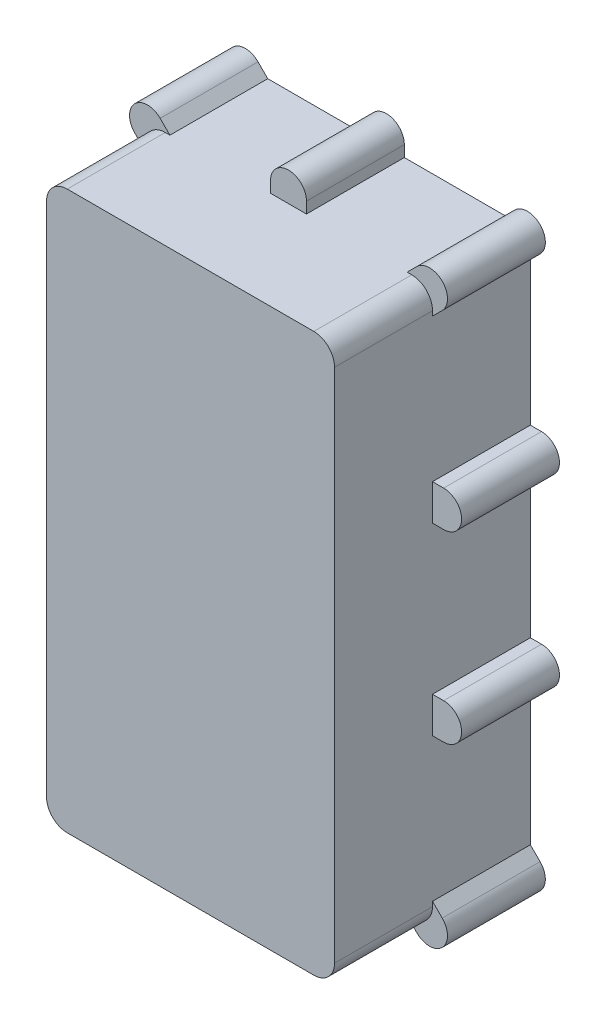
SolidWorks part; units mm, degrees
material "ABS"
ref_plane "X-Y Datum" through (0, 0, 0) normal (0, 0, 1) x (1, 0, 0)
ref_plane "X-Z Datum" through (0, 0, 0) normal (0, 1, 0) x (1, 0, 0)
ref_plane "Y-Z Datum" through (0, 0, 0) normal (1, 0, 0) x (0, 0, -1)
sketch "Sketch1" plane through (0, 0, 0) normal (0, 0, 1) x (1, 0, 0)
  line L0 (1.8162, 48.1563) -> (125.4513, 48.1563) construction
  line L1 (24.3593, 48.1563) -> (24.3593, 120.2923) construction
  line L3 (24.3593, 120.2923) -> (125.4513, 120.2923) construction
  line L8 (125.4513, 48.1563) -> (125.4513, 120.2923) construction
  line L33 (24.3593, 120.2923) -> (1.8162, 120.2923) construction
  line L34 (24.3593, 120.2923) -> (24.3593, 48.1563) construction
  line L35 (63.6337, 48.1563) -> (63.6337, 43.0763) construction
  line L36 (1.8162, 120.2923) -> (1.8162, 48.1563) construction
  line L41 (24.3593, 120.2923) -> (23.7243, 120.2923) construction
  line L42 (24.3593, 120.2923) -> (24.3593, 122.8323) construction
  line L44 (27.5343, 14.7553) -> (27.5343, 43.0763) construction
  line L45 (125.4513, 120.2923) -> (127.9913, 120.2923) construction
  line L46 (27.5343, 14.7553) -> (125.4513, 14.7553) construction
  line L47 (23.7243, 122.8323) -> (127.9913, 122.8323)
  line L48 (23.7243, 122.8323) -> (23.7243, -21.9477)
  line L49 (23.7243, -21.9477) -> (127.9913, -21.9477)
  line L50 (127.9913, 122.8323) -> (127.9913, -21.9477)
  line L51 (125.4513, 14.7553) -> (125.4513, 43.0763) construction
  line L52 (27.5343, 43.0763) -> (125.4513, 43.0763) construction
  line L53 (23.7243, 120.2923) -> (23.7243, 48.1563) construction
  circle A17 centre (30.4553, 114.1963) radius 2.1 construction
  circle A18 centre (119.8633, 115.2123) radius 2.1 construction
  circle A19 centre (119.6813, 54.2533) radius 2.1 construction
  circle A20 centre (29.4393, 53.2363) radius 2.1 construction
  circle A26 centre (31.9793, 18.4383) radius 2.1 construction
  circle A27 centre (31.9793, 39.3933) radius 2.1 construction
  circle A28 centre (120.6193, 28.8183) radius 2.1 construction
sketch "Sketch2" plane through (0, 0, 0) normal (0, 0, 1) x (1, 0, 0)
  line L4 (55.176, 122.8323) -> (127.9913, 122.8323)
  line L6 (55.176, 48.5244) -> (55.176, 50.9244) construction
  line L7 (55.176, -21.05) -> (127.9913, -21.05)
  line L8 (127.9913, 122.8323) -> (127.9913, -21.05)
  line L9 (55.176, 110.2103) -> (127.9913, -21.05) construction
  line L10 (55.176, -8.428) -> (127.9913, 122.8323) construction
  line L11 (55.176, 50.9244) -> (55.176, -21.05)
  line L12 (55.176, 50.9244) -> (55.176, 122.8323)
  circle A7 centre (88.0827, 6.45) radius 27.5
  circle A8 centre (88.0294, 95.3501) radius 27.5
  circle A9 centre (98.216, 50.8911) radius 6.477
  circle A10 centre (77.896, 50.9089) radius 6.477
  circle A11 centre (121.5143, 31.8208) radius 6.477
  circle A12 centre (115.996, 50.8756) radius 2.4
  circle A13 centre (55.176, 50.9244) radius 2.4
  point P14 (88.0827, 50.8911)
sketch "Sketch3" plane through (0, 0, 0) normal (0, 0, 1) x (1, 0, 0)
  line L7 (0, 0) -> (76.2, 0)
  line L10 (0, 0) -> (0, 158.75)
  line L11 (0, 158.75) -> (76.2, 158.75)
  line L12 (76.2, 0) -> (76.2, 158.75)
  dimension "D1" = 158.75
  dimension "D2" = 76.2
extrude "Boss-Extrude1" add sketch "Sketch3" along normal blind 53.975
shell "Shell1" thickness 6 removed face at (38.1, 79.375, 0) outward yes
fillet "Fillet1" radius 5.334 4 edges at (76.2, 158.75, 26.9875) (76.2, 0, 26.9875) (0, 0, 26.9875) (0, 158.75, 26.9875)
fillet "Fillet2" radius 6.35 4 edges at (-6, -6, 29.9875) (-6, 164.75, 29.9875) (82.2, 164.75, 29.9875) (82.2, -6, 29.9875)
sketch "Sketch6" plane through (0, 0, 0) normal (0, 0, -1) x (-1, 0, 0)
  line L8 (-5.334, 163.0327) -> (-70.866, 163.0327)
  line L9 (-80.4827, 153.416) -> (-80.4827, 5.334)
  line L10 (-70.866, -4.2827) -> (-5.334, -4.2827)
  line L11 (4.2827, 5.334) -> (4.2827, 153.416)
  line L12 (-79.2, 153.416) -> (-79.2, 5.334)
  line L13 (-70.866, -3) -> (-5.334, -3)
  line L14 (3, 5.334) -> (3, 153.416)
  line L15 (-5.334, 161.75) -> (-70.866, 161.75)
  line L16 (-79.2, 153.416) -> (-79.2, 5.334) construction
  line L17 (-70.866, -3) -> (-5.334, -3) construction
  line L18 (3, 5.334) -> (3, 153.416) construction
  line L19 (-5.334, 161.75) -> (-70.866, 161.75) construction
  line L20 (-77.9173, 153.416) -> (-77.9173, 5.334)
  line L21 (-70.866, -1.7173) -> (-5.334, -1.7173)
  line L22 (1.7173, 5.334) -> (1.7173, 153.416)
  line L23 (-5.334, 160.4673) -> (-70.866, 160.4673)
  arc A8 (-70.866, 163.0327) -> (-80.4827, 153.416) centre (-70.866, 153.416) ccw
  arc A9 (-80.4827, 5.334) -> (-70.866, -4.2827) centre (-70.866, 5.334) ccw
  arc A10 (-5.334, -4.2827) -> (4.2827, 5.334) centre (-5.334, 5.334) ccw
  arc A11 (4.2827, 153.416) -> (-5.334, 163.0327) centre (-5.334, 153.416) ccw
  arc A12 (-70.866, 161.75) -> (-79.2, 153.416) centre (-70.866, 153.416) ccw
  arc A13 (-79.2, 5.334) -> (-70.866, -3) centre (-70.866, 5.334) ccw
  arc A14 (-5.334, -3) -> (3, 5.334) centre (-5.334, 5.334) ccw
  arc A15 (3, 153.416) -> (-5.334, 161.75) centre (-5.334, 153.416) ccw
  arc A16 (-70.866, 161.75) -> (-79.2, 153.416) centre (-70.866, 153.416) ccw construction
  arc A17 (-79.2, 5.334) -> (-70.866, -3) centre (-70.866, 5.334) ccw construction
  arc A18 (-5.334, -3) -> (3, 5.334) centre (-5.334, 5.334) ccw construction
  arc A19 (3, 153.416) -> (-5.334, 161.75) centre (-5.334, 153.416) ccw construction
  arc A20 (-77.9173, 5.334) -> (-70.866, -1.7173) centre (-70.866, 5.334) ccw
  arc A21 (-5.334, -1.7173) -> (1.7173, 5.334) centre (-5.334, 5.334) ccw
  arc A22 (1.7173, 153.416) -> (-5.334, 160.4673) centre (-5.334, 153.416) ccw
  arc A23 (-70.866, 160.4673) -> (-77.9173, 153.416) centre (-70.866, 153.416) ccw
  dimension "D4" = 7.0513
  dimension "D5" = 2.5654
  dimension "D1" = 3
  dimension "D2" = 1.2827
  dimension "D3" = 1.2827
extrude "Cut-Extrude1" cut sketch "Sketch6" against normal blind 1.2446
fillet "Fillet3" radius 0.254 16 edges at (-4.2827, 79.375, 1.2446) (-1.466, -1.466, 1.2446) (38.1, -4.2827, 1.2446) (77.666, -1.466, 1.2446) (80.4827, 79.375, 1.2446) (77.666, 160.216, 1.2446) (38.1, 163.0327, 1.2446) (-1.466, 160.216, 1.2446) (75.852, 158.402, 1.2446) (77.9173, 79.375, 1.2446) (75.852, 0.348, 1.2446) (38.1, -1.7173, 1.2446) (0.348, 0.348, 1.2446) (-1.7173, 79.375, 1.2446) (0.348, 158.402, 1.2446) (38.1, 160.4673, 1.2446)
fillet "Fillet4" radius 0.127 16 edges at (75.852, 158.402, 0) (38.1, 160.4673, 0) (0.348, 158.402, 0) (-1.7173, 79.375, 0) (0.348, 0.348, 0) (38.1, -1.7173, 0) (75.852, 0.348, 0) (77.666, 160.216, 0) (38.1, 163.0327, 0) (-1.466, 160.216, 0) (-4.2827, 79.375, 0) (-1.466, -1.466, 0) (38.1, -4.2827, 0) (77.666, -1.466, 0) (77.9173, 79.375, 0) (80.4827, 79.375, 0)
sketch "Sketch7" plane through (0, 0, 53.975) normal (0, 0, -1) x (-1, 0, 0)
  line L0 (-76.2, 34.925) -> (0, 34.925)
  line L1 (-76.2, 5.334) -> (-76.2, 153.416) construction
  line L2 (0, 153.416) -> (0, 5.334) construction
  line L3 (-76.2, 37.425) -> (0, 37.425)
  line L4 (-5.334, 0) -> (-70.866, 0) construction
  line L5 (-76.2, 34.925) -> (-76.2, 37.425)
  line L6 (0, 34.925) -> (0, 37.425)
  dimension "D2" = 34.925
  dimension "D1" = 2.5
extrude "Boss-Extrude2" add sketch "Sketch7" along normal up to surface (53.975 mm away) up to face at (38.1, 79.375, 0)
sketch "Sketch8" plane through (0, 0, 0) normal (0, 0, -1) x (-1, 0, 0)
  line L0 (-5.334, 5.334) -> (5.0914, -5.0914)
  line L1 (-1.7782, -6) -> (1.2023, -8.9805)
  line L2 (-0.35, -6) -> (-75.85, -6) construction
  line L3 (-5.334, -4.2827) -> (-5.334, -4.4097)
  line L4 (4.4097, 5.334) -> (4.2827, 5.334)
  line L5 (-5.334, -4.2827) -> (-5.334, -4.4097)
  line L6 (4.4097, 5.334) -> (4.2827, 5.334)
  line L7 (6, 1.7782) -> (8.9805, -1.2023)
  line L8 (6, 158.4) -> (6, 0.35) construction
  line L9 (-38.1, -6) -> (-38.1, 164.75) construction
  line L10 (-75.85, 164.75) -> (-0.35, 164.75) construction
  line L11 (-82.2, 79.375) -> (6, 79.375) construction
  line L12 (-82.2, 0.35) -> (-82.2, 158.4) construction
  circle A0 centre (5.0914, -5.0914) radius 3.025
  circle A1 centre (5.0914, -5.0914) radius 5.5
  arc A3 (-5.334, -4.4097) -> (4.4097, 5.334) centre (-5.334, 5.334) ccw
  arc A4 (-5.334, -4.2827) -> (4.2827, 5.334) centre (-5.334, 5.334) ccw
  arc A5 (-5.334, -4.4097) -> (4.4097, 5.334) centre (-5.334, 5.334) ccw
  arc A6 (-5.334, -4.2827) -> (4.2827, 5.334) centre (-5.334, 5.334) ccw
  point P6 (1.5558, -1.5558)
  dimension "D1" = 6.05
  dimension "D4" = 11
  dimension "D3" = 5
  dimension "D2" = 0
extrude "Boss-Extrude3" add sketch "Sketch8" against normal blind 29.972
sketch "Sketch9" plane through (0, 0, 0) normal (0, 0, -1) x (-1, 0, 0)
  circle A0 centre (5.0914, -5.0914) radius 3.025 construction
  circle A1 centre (5.0914, -5.0914) radius 3.025
  dimension "D1" = 6.05
extrude "Cut-Extrude2" cut sketch "Sketch9" against normal blind 9
ref_plane "Plane1" through (38.1, 0, 0) normal (-1, 0, 0) x (0, 0, 1)
ref_plane "Plane2" through (0, 79.375, 0) normal (0, -1, 0) x (-1, 0, 0)
mirror "Mirror1" about plane through (38.1, 0, 0) normal (-1, 0, 0) of "Cut-Extrude2", "Boss-Extrude3"
mirror "Mirror2" about plane through (0, 79.375, 0) normal (0, -1, 0) of "Cut-Extrude2", "Boss-Extrude3", "Mirror1"
sketch "Sketch10" plane through (0, 0, 0) normal (0, 0, -1) x (-1, 0, 0)
  line L0 (6, 79.375) -> (39.3327, 79.375) construction
  line L2 (6, 156.9718) -> (6, 1.7782) construction
  line L3 (6, 79.375) -> (6, 157.4914)
  line L4 (6, 107.569) -> (9.4097, 107.569) construction
  line L5 (4.4097, 153.416) -> (4.4097, 5.334) construction
  line L7 (9.4097, 113.069) -> (6, 113.069)
  line L9 (9.4097, 102.069) -> (6, 102.069)
  line L10 (9.4097, 45.681) -> (6, 45.681)
  line L11 (9.4097, 56.681) -> (6, 56.681)
  circle A4 centre (9.4097, 107.569) radius 3.025
  circle A5 centre (9.4097, 107.569) radius 5.5
  circle A6 centre (9.4097, 51.181) radius 3.025
  circle A7 centre (9.4097, 51.181) radius 5.5
  point P0 (5.0914, 163.8414)
  point P1 (5.0914, -5.0914)
  point P3 (-81.2914, -5.0914)
  dimension "D3" = 84.4664
  dimension "D4" = 6.05
  dimension "D5" = 11
  dimension "D1" = 168.9327
  dimension "D2" = 86.3827
  dimension "D6" = 5
  dimension "D7" = 28.194
  dimension "D8" = 56.2724
  dimension "D9" = 56.388
  dimension "D10" = 56.2724
extrude "Boss-Extrude4" add sketch "Sketch10" against normal blind 29.972
sketch "Sketch11" plane through (0, 0, 0) normal (0, 0, -1) x (-1, 0, 0)
  circle A0 centre (9.4097, 51.181) radius 3.025 construction
  circle A1 centre (9.4097, 107.569) radius 3.025 construction
  circle A2 centre (9.4097, 51.181) radius 3.025
  circle A3 centre (9.4097, 107.569) radius 3.025
  dimension "D1" = 6.05
extrude "Cut-Extrude3" cut sketch "Sketch11" against normal blind 9
mirror "Mirror3" about plane through (38.1, 0, 0) normal (-1, 0, 0) of "Cut-Extrude3", "Boss-Extrude4"
sketch "Sketch12" plane through (0, 0, 0) normal (0, 0, -1) x (-1, 0, 0)
  line L0 (-74.4218, -6) -> (-1.7782, -6)
  line L1 (-38.1, -6) -> (-38.1, -9.4097) construction
  line L2 (-5.334, -4.4097) -> (-70.866, -4.4097) construction
  line L3 (-43.6, -9.4097) -> (-43.6, -6)
  line L4 (-32.6, -9.4097) -> (-32.6, -6)
  circle A0 centre (-38.1, -9.4097) radius 3.025
  circle A1 centre (-38.1, -9.4097) radius 5.5
  point P15 (-81.2914, -5.0914)
  point P16 (5.0914, -5.0914)
  dimension "D2" = 6.05
  dimension "D4" = 11
  dimension "D1" = 43.1914
  dimension "D3" = 5
  dimension "D5" = 86.3827
extrude "Boss-Extrude5" add sketch "Sketch12" against normal blind 29.972
sketch "Sketch13" plane through (0, 0, 0) normal (0, 0, -1) x (-1, 0, 0)
  circle A0 centre (-38.1, -9.4097) radius 3.025 construction
  circle A1 centre (-38.1, -9.4097) radius 3.025
extrude "Cut-Extrude4" cut sketch "Sketch13" against normal blind 9
mirror "Mirror4" about plane through (0, 79.375, 0) normal (0, -1, 0) of "Cut-Extrude4", "Boss-Extrude5"
sketch "Sketch17" plane through (-6, 0, 0) normal (-1, 0, 0) x (0, 0, 1)
  line L0 (59.975, 158.4) -> (59.975, 0.35) construction
  line L1 (0, 37.425) -> (53.975, 37.425) construction
  line L2 (53.975, 34.925) -> (53.975, 5.334) construction
  circle A0 centre (38.385, 119.975) radius 9.525
  circle A1 centre (38.385, 119.975) radius 14.2875
  circle A2 centre (38.385, 20.1295) radius 6.35
  circle A3 centre (38.385, 20.1295) radius 10.795
  point P10 (53.975, 20.1295)
  dimension "D1" = 19.05
  dimension "D4" = 28.575
  dimension "D5" = 12.7
  dimension "D6" = 21.59
  dimension "D2" = 21.59
  dimension "D3" = 82.55
extrude "Cut-Extrude6" cut sketch "Sketch17" against normal blind 6 contours A0 | A2
sketch "Sketch18" plane through (0, 0, 0) normal (1, 0, 0) x (0, 0, -1)
  circle A0 centre (-38.385, 119.975) radius 14.2875 construction
  circle A1 centre (-38.385, 119.975) radius 14.2875
  circle A2 centre (-38.385, 20.1295) radius 10.795 construction
  circle A3 centre (-38.385, 20.1295) radius 10.795
extrude "Cut-Extrude7" cut sketch "Sketch18" against normal blind 3
